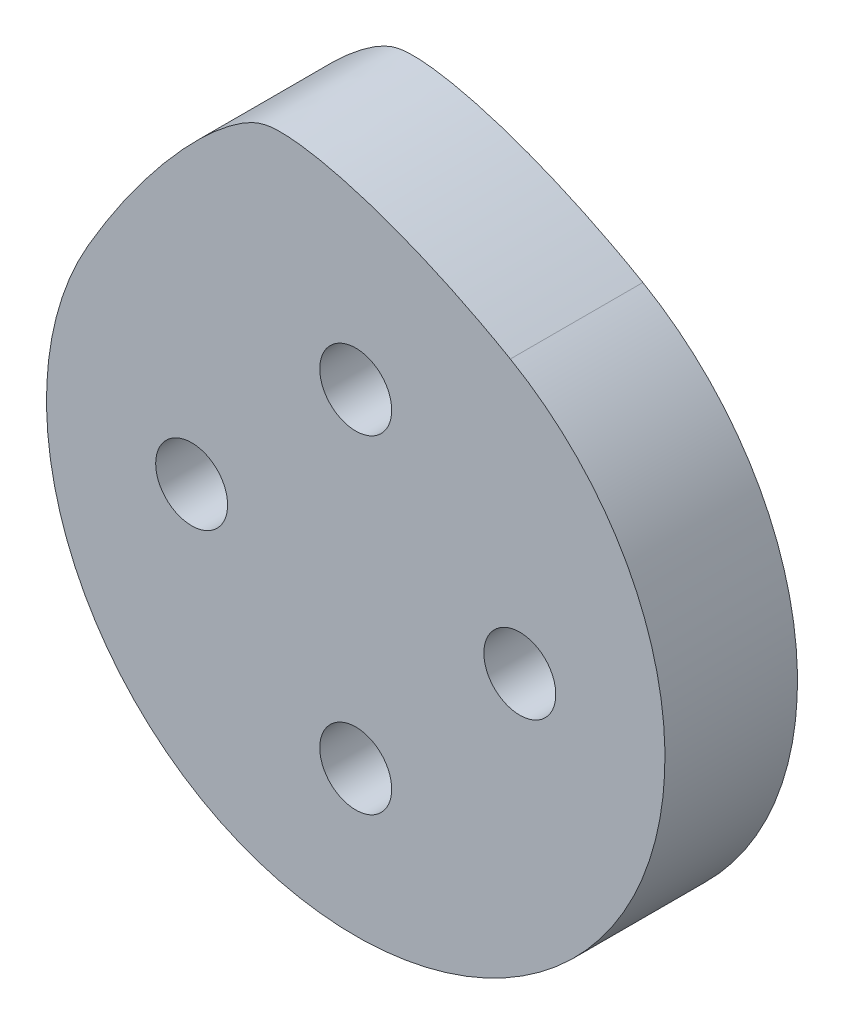
SolidWorks part; units mm, degrees
ref_plane "Front Plane" through (0, 0, 0) normal (1, 0, 0) x (0, 1, 0)
ref_plane "Top Plane" through (0, 0, 0) normal (0, 0, 1) x (0, 1, 0)
ref_plane "Right Plane" through (0, 0, 0) normal (0, 1, 0) x (-1, 0, 0)
sketch "Sketch1" plane through (0, 0, 0) normal (0, 0, 1) x (0, 1, 0)
  circle A0 centre (0, 0) radius 21
  circle A1 centre (0, 0) radius 13 construction
  circle A2 centre (0, 13) radius 1.6
  circle A3 centre (0, 13) radius 2.85
  circle A4 centre (13, 0) radius 2.85
  circle A5 centre (13, 0) radius 1.6
  circle A6 centre (0, -13) radius 2.85
  circle A7 centre (0, -13) radius 1.6
  circle A8 centre (-13, 0) radius 2.85
  circle A9 centre (-13, 0) radius 1.6
  point P19 (0, 0)
  dimension "D1" = 42
  dimension "D2" = 26
  dimension "D3" = 3.2
  dimension "D4" = 5.7
  dimension "D5" = 4
extrude "Boss-Extrude1" add sketch "Sketch1" along normal blind 10.5 contours A0 A8 A6 A4 A3 | A8 A9 | A3 A2 | A4 A5 | A6 A7 region at (0, 0, 0) region at (-13, -2.7694, 0) region at (0, 10.2306, 0) region at (13, -2.7694, 0) region at (0, -15.7694, 0)
sketch "Sketch2" plane through (0, 0, 0) normal (0, 0, -1) x (1, 0, 0)
  line L0 (0, 0) -> (0, 28.5) construction
  line L1 (0, 0) -> (-7.3763, -27.5289) construction
  line L2 (0, 0) -> (-24.6817, -14.25) construction
  line L3 (0, 0) -> (14.25, -24.6817) construction
  line L4 (-9.1462, -27.0547) -> (-47.7832, -16.7019) construction
  line L5 (-0.6017, -47.9579) -> (-60.6017, 55.9652) construction
  line L6 (47.9579, -0.6017) -> (-55.9652, -60.6017) construction
  circle A0 centre (0, 0) radius 28.5 construction
  circle A1 centre (0, 0) radius 24.5
  spline S0 degree 3 poles (-21.2176, -12.25) (-16.7176, -20.0442) (-10.224, -26.8074) (-4.5495, -28.3279) (4.4558, -25.7176) (12.25, -21.2176) knots 0 0 0 0 0.45 0.55 1 1 1 1
  circle M5 centre (0, 0) radius 21
  dimension "D1" = 57
  dimension "D2" = 49
  dimension "D6" = 20
  dimension "D7" = 30
  dimension "D8" = 30
  dimension "D3" = 195
  dimension "D4" = 45
  dimension "D5" = 45
  dimension "D9" = 90
  dimension "D10" = 90
  dimension "D11" = 90
extrude "Boss-Extrude3" add sketch "Sketch2" against normal up to surface (10.5 mm away) contours A1 M5 | A1 S0 region at (20.6175, 11.9035, 0) region at (-6.4986, 24.241, 0) up to face at (21, 0, 10.5)
sketch "Sketch3" plane through (0, 0, 0) normal (0, 0, -1) x (1, 0, 0)
  circle A0 centre (0, 0) radius 21
  circle A5 centre (-13, 0) radius 1.6
  circle A6 centre (0, 13) radius 1.6
  circle A7 centre (13, 0) radius 1.6
  circle A8 centre (0, -13) radius 1.6
  dimension "D1" = 42
extrude "Boss-Extrude4" add sketch "Sketch3" along normal blind 0.5
sketch "Sketch4" plane through (0, 0, 10.5) normal (0, 0, 1) x (1, 0, 0)
  circle A5 centre (-13, 0) radius 1.6
  circle A6 centre (0, 13) radius 1.6
  circle A7 centre (13, 0) radius 1.6
  circle A8 centre (0, -13) radius 1.6
  circle A9 centre (0, 13) radius 2.85
  circle A10 centre (13, 0) radius 2.85
  circle A11 centre (0, -13) radius 2.85
  circle A12 centre (-13, 0) radius 2.85
  dimension "D1" = 5.7
  dimension "D2" = 5.7
  dimension "D3" = 5.7
  dimension "D4" = 5.7
extrude "Cut-Extrude1" cut sketch "Sketch4" against normal blind 8.5 and the other way through all
